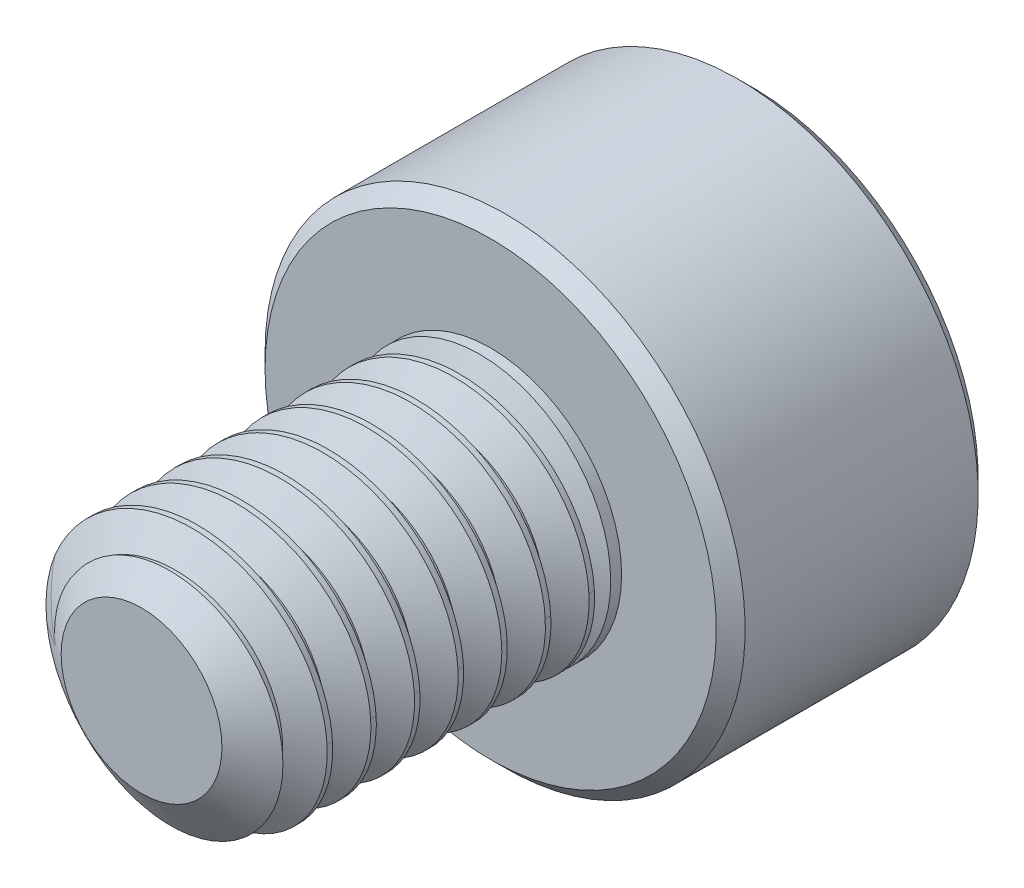
SolidWorks part; units mm, degrees
ref_plane "Front Plane" through (0, 0, 0) normal (0, 0, 1) x (1, 0, 0)
ref_plane "Top Plane" through (0, 0, 0) normal (0, 1, 0) x (1, 0, 0)
ref_plane "Right Plane" through (0, 0, 0) normal (1, 0, 0) x (0, 0, -1)
sketch "Sketch1" plane through (0, 0, 0) normal (0, 0, 1) x (1, 0, 0)
  circle A0 centre (0, 0) radius 1.5
  dimension "OD" = 3
extrude "Extrude1" add sketch "Sketch1" against normal blind 4
sketch "Sketch2" plane through (0, 0, 0) normal (0, 0, 1) x (1, 0, 0)
  circle A0 centre (0, 0) radius 1.5 construction
  circle A1 centre (0, 0) radius 1.5
curve "Helix/Spiral1" pitch 0.5 height 4.5 radius 1.5 centre (0, 0, 0) axis (0, 0, -1) start towards (0, 1, 0) parameters "pitch"=0.5
sketch "Sketch3" plane through (0, 0, 0) normal (1, 0, 0) x (0, 0, -1)
  line L0 (-0.4375, 1.5) -> (-0.25, 1.1752)
  line L1 (-0.25, 1.1752) -> (-0.1875, 1.1752)
  line L2 (-0.1875, 1.1752) -> (0, 1.5)
  line L3 (-0.4375, 1.5) -> (0, 1.5)
  line L4 (-0.2187, 1.5) -> (-0.2187, 1.1752) construction
  line L5 (-0.3437, 1.3376) -> (-0.0937, 1.3376) construction
  line L6 (0, 1.5) -> (0, -1.5) construction
  line L7 (0, -1.5) -> (4, -1.5) construction
  point P11 (2.25, -1.5)
  dimension "D1" = 0.0625
  dimension "D2" = 0.25
  dimension "D3" = 60
  dimension "D4" = 2.25
sweep "Cut-Sweep1" cut profiles "Sketch3" path "Helix/Spiral1"
sketch "Sketch4" plane through (0, 0, 0) normal (1, 0, 0) x (0, 0, -1)
  line L0 (0.4053, 1.5) -> (0, 0.9212)
  line L1 (0, 0.9212) -> (0, 1.5)
  line L2 (0.4053, 1.5) -> (0, 1.5)
  line L3 (-0.4375, 1.5) -> (0, 1.5) construction
  line L4 (0, 0) -> (7.0209, 0) construction
  dimension "D1" = 55
  dimension "D2" = 0.254
revolve "Cut-Revolve1" cut sketch "Sketch4" angle 360 about L4
sketch "Sketch5" plane through (0, 0, 0) normal (1, 0, 0) x (0, 0, -1)
  line L0 (4, -1.1822) -> (4, 1.0703) construction
  line L1 (4, 1.5) -> (0.1203, 1.5)
  line L2 (4, 1.5) -> (4, 0)
  line L3 (4, 0) -> (0.0001, 0)
  line L4 (0.0001, 1.1698) -> (0.0001, 0)
  line L5 (0.1203, 1.5) -> (0.0001, 1.1698)
  line L6 (0, 0) -> (9.9695, 0) construction
  point P3 (0.0001, 1.5)
  point P10 (0.0001, 1.5)
  dimension "D1" = 0.3302
  dimension "Thread min" = 0.0001
  dimension "D3" = 20
revolve "partially thread" [suppressed] add sketch "Sketch5" angle 360 about L6
sketch "Sketch6" plane through (0, 0, -4) normal (0, 0, -1) x (-1, 0, 0)
  circle A0 centre (0, 0) radius 2.75
  dimension "head dia" = 5.5
extrude "Extrude2" add sketch "Sketch6" along normal blind 3
sketch "Sketch7" plane through (0, 0, -7) normal (0, 0, -1) x (-1, 0, 0)
  line L1 (0, 1.4434) -> (-1.25, 0.7217)
  line L2 (-1.25, 0.7217) -> (-1.25, -0.7217)
  line L3 (-1.25, -0.7217) -> (0, -1.4434)
  line L4 (0, -1.4434) -> (1.25, -0.7217)
  line L5 (1.25, -0.7217) -> (1.25, 0.7217)
  line L6 (1.25, 0.7217) -> (0, 1.4434)
  circle A0 centre (0, 0) radius 1.25 construction
  dimension "hex dia" = 2.5
extrude "Cut-Extrude1" cut sketch "Sketch7" against normal blind 1.875
sketch "Sketch8" plane through (0, 0, -7) normal (0, 0, -1) x (-1, 0, 0)
  circle A0 centre (0, 0) radius 1.4434
extrude "Cut-Extrude2" cut sketch "Sketch8" against normal through all draft 45
chamfer "Chamfer1" distance 0.165 angle 45 2 edges at (-2.75, 0, -7) (-2.75, 0, -4)
sketch "Sketch9" plane through (0, 0, 0) normal (1, 0, 0) x (0, 0, -1)
  line L0 (0, 1.5) -> (0, -1.5) construction
  line L1 (2.75, 1.5) -> (2.75, -1.5) construction
  dimension "D1" = 2.75
sketch "Sketch10" plane through (0, 0, 0) normal (1, 0, 0) x (0, 0, -1)
  line L0 (4, 1.5) -> (4, 0)
  line L1 (4, 1.5) -> (3.875, 1.5)
  line L2 (3.875, 1.5) -> (3.2537, 0)
  line L3 (4, 0) -> (3.2537, 0)
  line L4 (4, 2.585) -> (4, -2.585) construction
  dimension "D1" = 22.5
  dimension "D2" = 0.125
revolve "Revolve1" add sketch "Sketch10" angle 360 about L3
equation "\"D3@Helix/Spiral1\" = \"screw length@Extrude1\"+\"pitch@Helix/Spiral1\""
equation "\"D1@Sketch3\" = \"pitch@Helix/Spiral1\"*.125"
equation "\"D2@Sketch3\" = \"pitch@Helix/Spiral1\"*.5"
equation "\"D1@Cut-Extrude1\" = \"hex dia@Sketch7\"*.75"
equation "\"D1@Chamfer1\" = \"head dia@Sketch6\"*.03"
equation "\"D1@Sketch9\" = \"pitch@Helix/Spiral1\"*5.5"
equation "\"D2@Sketch10\" = \"pitch@Helix/Spiral1\"*.25"
equation "\"D4@Sketch3\" = \"pitch@Helix/Spiral1\"*4.50"
